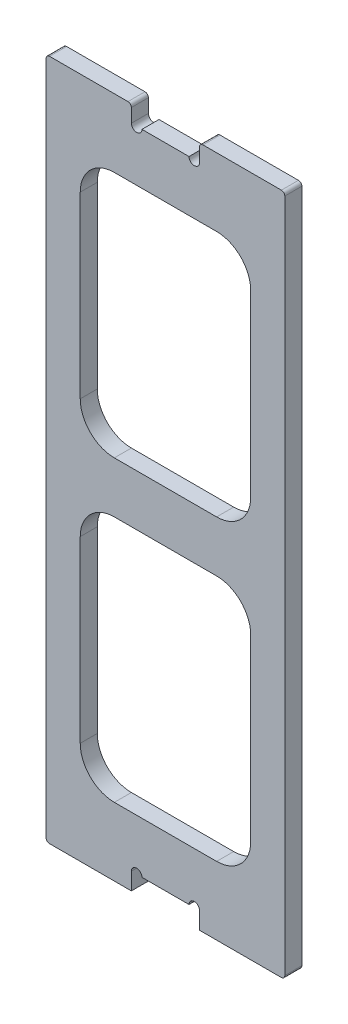
SolidWorks part; units mm, degrees
material "Hexcel AS4C (3000 丝)"
ref_plane "前视基准面" through (0, 0, 0) normal (0, 0, 1) x (1, 0, 0)
ref_plane "上视基准面" through (0, 0, 0) normal (0, 1, 0) x (1, 0, 0)
ref_plane "右视基准面" through (0, 0, 0) normal (1, 0, 0) x (0, 0, -1)
other "Configuration Table"
sketch "草图1" plane through (0, 0, 0) normal (0, 0, 1) x (1, 0, 0)
  line L1 (0, 0) -> (70, 0)
  line L2 (0, 0) -> (0, 190)
  line L3 (0, 190) -> (70, 190)
  line L4 (70, 0) -> (70, 190)
  line L5 (45, 0) -> (70, 0)
  line L6 (45, 0) -> (45, -5)
  line L7 (45, -5) -> (70, -5)
  line L8 (70, 0) -> (70, -5)
  line L9 (0, 0) -> (25, 0)
  line L10 (0, 0) -> (0, -5)
  line L11 (0, -5) -> (25, -5)
  line L12 (25, 0) -> (25, -5)
  line L13 (70, 190) -> (45, 190)
  line L14 (70, 190) -> (70, 195)
  line L15 (70, 195) -> (45, 195)
  line L16 (45, 190) -> (45, 195)
  line L17 (0, 190) -> (25, 190)
  line L18 (0, 190) -> (0, 195)
  line L19 (0, 195) -> (25, 195)
  line L20 (25, 190) -> (25, 195)
  dimension "D1" = 70
  dimension "D2" = 190
  dimension "D3" = 25
  dimension "D4" = 25
  dimension "D5" = 5
  dimension "D6" = 5
  dimension "D7" = 25
  dimension "D8" = 25
  dimension "D9" = 5
  dimension "D10" = 5
extrude "凸台-拉伸1" add sketch "草图1" along normal blind 5 contours L16 L3 L14 L15 | L1 L4 L3 L2 | L3 L20 L19 L18 | L8 L1 L6 L7 | L12 L1 L10 L11 region at (35, 95, 0) region at (12.5, -2.5, 0) region at (12.5, 192.5, 0) region at (57.5, -2.5, 0) region at (57.5, 192.5, 0)
sketch "草图2" plane through (0, 0, 5) normal (0, 0, 1) x (1, 0, 0)
  line L0 (25, 0) -> (45, 0) construction
  line L1 (45, 0) -> (45, -5) construction
  line L2 (25, 0) -> (25, -5) construction
  line L3 (25, 190) -> (45, 190) construction
  line L4 (25, 190) -> (25, 195) construction
  line L5 (45, 190) -> (45, 195) construction
  circle A0 centre (43.45, 0) radius 1.55
  circle A1 centre (26.55, 0) radius 1.55
  circle A2 centre (43.45, 190) radius 1.55
  circle A3 centre (26.55, 190) radius 1.55
  dimension "D4" = 3.1
extrude "切除-拉伸1" cut sketch "草图2" against normal blind 5
sketch "草图3" plane through (0, 0, 5) normal (0, 0, 1) x (1, 0, 0)
  line L0 (-53.1567, 95) -> (111.5166, 95) construction
  line L1 (35, -9.6754) -> (35, 200.1889) construction
  line L2 (70, -5) -> (70, 195) construction
  line L3 (0, -5) -> (0, 195) construction
  line L4 (45, -5) -> (70, -5) construction
  line L5 (70, 195) -> (45, 195) construction
  line L6 (28.1, 0) -> (41.9, 0) construction
  line L7 (10, 87.5) -> (60, 87.5)
  line L8 (10, 87.5) -> (10, 15)
  line L9 (10, 15) -> (60, 15)
  line L10 (60, 87.5) -> (60, 15)
  line L11 (10, 175) -> (60, 175)
  line L12 (10, 102.5) -> (60, 102.5)
  line L13 (10, 102.5) -> (10, 175)
  line L14 (60, 102.5) -> (60, 175)
  dimension "D1" = 7.5
  dimension "D2" = 10
  dimension "D3" = 10
  dimension "D4" = 15
extrude "切除-拉伸2" cut sketch "草图3" against normal up to surface (5 mm away) up to face at (35, 95, 0)
fillet "圆角1" radius 10 8 edges at (10, 15, 2.5) (60, 15, 2.5) (60, 87.5, 2.5) (10, 87.5, 2.5) (10, 102.5, 2.5) (60, 102.5, 2.5) (10, 175, 2.5) (60, 175, 2.5)
fillet "圆角2" radius 1 6 edges at (25, 195, 2.5) (45, 195, 2.5) (0, 195, 2.5) (70, 195, 2.5) (0, -5, 2.5) (70, -5, 2.5)
